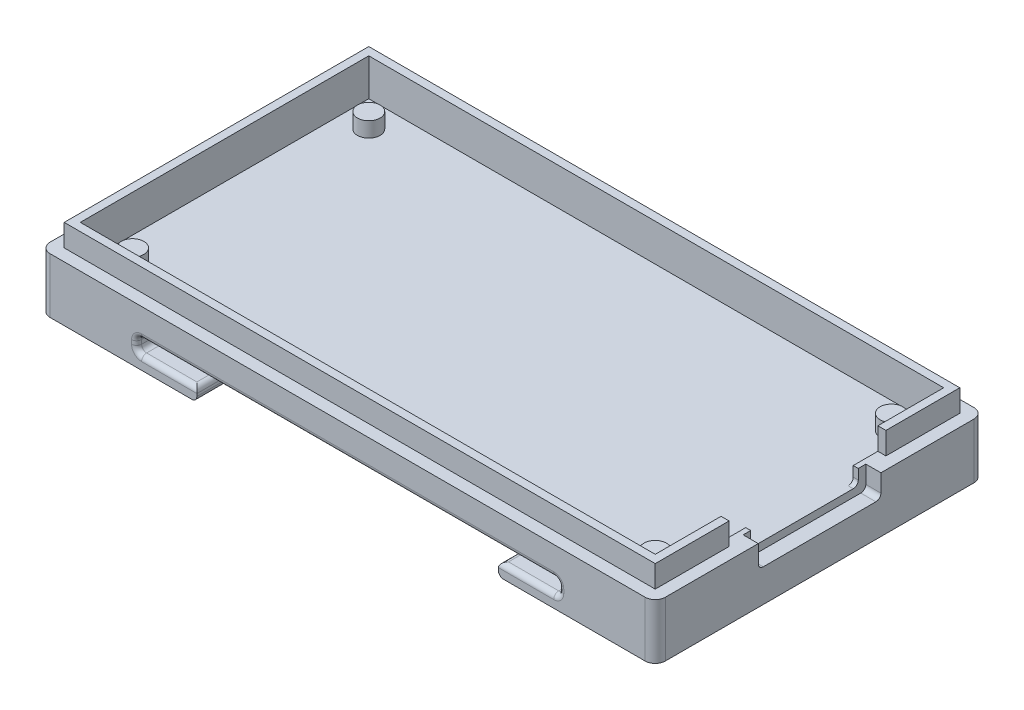
SolidWorks part; units mm, degrees
note: The reader was unsure of these and kept them because the rebuilt part matched: shared geometry of "Sketch2<3>", "Sketch2<4>", "Sketch3<4>", "Sketch2<5>".
ref_plane "Front Plane" through (0, 0, 0) normal (0, 0, 1) x (1, 0, 0)
ref_plane "Top Plane" through (0, 0, 0) normal (0, 1, 0) x (1, 0, 0)
ref_plane "Right Plane" through (0, 0, 0) normal (1, 0, 0) x (0, 0, -1)
sketch "Sketch2" plane through (0, 0, 0) normal (0, 1, 0) x (1, 0, 0)
  line L0 (0, 14.25) -> (0, -14.25) construction
  line L1 (-28.5, -14.25) -> (28.5, -14.25)
  line L2 (-28.5, -14.25) -> (-28.5, 14.25)
  line L3 (-28.5, 14.25) -> (28.5, 14.25)
  line L4 (28.5, -14.25) -> (28.5, 14.25)
  line L5 (-28.5, -14.25) -> (28.5, 14.25) construction
  line L6 (-28.5, 14.25) -> (28.5, -14.25) construction
  line L7 (-28.5, 0) -> (28.5, 0) construction
  line L8 (-30.6, -16.35) -> (-30.6, 16.35)
  line L9 (-28.6, -14.35) -> (28.6, -14.35)
  line L10 (-28.6, -14.35) -> (-28.6, 14.35)
  line L11 (-28.6, 14.35) -> (28.6, 14.35)
  line L12 (28.6, -14.35) -> (28.6, 14.35)
  line L13 (-28.6, -14.35) -> (28.6, 14.35) construction
  line L14 (-28.6, 14.35) -> (28.6, -14.35) construction
  line L15 (-30.6, 16.35) -> (30.6, 16.35)
  line L16 (30.6, -16.35) -> (30.6, 16.35)
  line L17 (-30.6, -16.35) -> (30.6, -16.35)
  line L19 (30.6, -5.35) -> (28.6, -5.35)
  line L20 (30.6, -5.35) -> (30.6, 5.35)
  line L21 (30.6, 5.35) -> (28.6, 5.35)
  line L22 (28.6, -5.35) -> (28.6, 5.35)
  line L31 (-30.6, 16.35) -> (30.6, 16.35) construction
  line L41 (30.6, 6.1) -> (29.1, 6.1)
  line L42 (30.6, 6.1) -> (30.6, -6.1)
  line L43 (30.6, -6.1) -> (29.1, -6.1)
  line L44 (29.1, 6.1) -> (29.1, -6.1)
  circle A0 centre (-26, 11.75) radius 1.125
  circle A1 centre (-26, -11.75) radius 1.125
  circle A2 centre (26, -11.75) radius 1.125
  circle A3 centre (26, 11.75) radius 1.125
  point P0 (0, 0)
  point P18 (0, 0)
  point P31 (30.2961, 16.35)
  dimension "D4" = 2.25
  dimension "D1" = 57
  dimension "D2" = 28.5
  dimension "D3" = 2.5
  dimension "D5" = 2.5
  dimension "D6" = 0.1
  dimension "D7" = 0.1
  dimension "D9" = 9
  dimension "D10" = 9
  dimension "D18" = 0.5
  dimension "D19" = 0.75
  dimension "D20" = 0.75
  dimension "D8" = 2
extrude "Boss-Extrude1" add sketch "Sketch2" along normal blind 1.5
extrude "Boss-Extrude2" add sketch "Sketch2<3>" along normal blind 1.5 from surface at 1.5
sketch "Sketch2<3>" plane through (0, 0, 0) normal (0, 1, 0) x (1, 0, 0) same geometry as "Sketch2"
extrude "Boss-Extrude3" add sketch "Sketch2<4>" against normal blind 2.5
sketch "Sketch2<4>" plane through (0, 0, 0) normal (0, 1, 0) x (1, 0, 0) same geometry as "Sketch2"
fillet "Fillet1" radius 1 4 edges at (-30.6, 0.25, -16.35) (-30.6, 0.25, 16.35) (30.6, 0.25, 16.35) (30.6, 0.25, -16.35)
sketch "Sketch3" plane through (0, 0, 0) normal (0, 0, 1) x (1, 0, 0)
  line L0 (30.6, 3) -> (30.6, -2.5) construction
  line L1 (-21, -1.25) -> (21, -1.25)
  line L2 (-21, -1.25) -> (-21, 0.15)
  line L3 (-21, 0.15) -> (21, 0.15)
  line L4 (21, -1.25) -> (21, 0.15)
  line L5 (-21, -1.25) -> (21, 0.15) construction
  line L6 (-21, 0.15) -> (21, -1.25) construction
  line L7 (30.6, 1.4) -> (-30.6, 1.4)
  line L8 (30.6, 1.4) -> (30.6, -2.5)
  line L9 (30.6, -2.5) -> (-30.6, -2.5)
  line L10 (-30.6, 1.4) -> (-30.6, -2.5)
  line L11 (30.6, 1.4) -> (-30.6, -2.5) construction
  line L12 (30.6, -2.5) -> (-30.6, 1.4) construction
  line L13 (-30.6, -2.5) -> (-30.6, 3) construction
  line L14 (-29.6, -2.5) -> (29.6, -2.5) construction
  line L16 (-10, -1.25) -> (10, -1.25)
  line L17 (-10, -1.25) -> (-10, -2.5)
  line L18 (-10, -2.5) -> (10, -2.5)
  line L19 (10, -1.25) -> (10, -2.5)
  line L20 (15, -2.5) -> (-15, -2.5)
  line L21 (15, -2.5) -> (15, -1.25)
  line L22 (15, -1.25) -> (-15, -1.25)
  line L23 (-15, -2.5) -> (-15, -1.25)
  point P0 (0, -0.55)
  point P5 (0, -0.55)
  point P20 (0, -1.25)
  point P26 (0, -2.5)
  dimension "D1" = 1.25
  dimension "D2" = 1.4
  dimension "D3" = 42
  dimension "D4" = 20
  dimension "D5" = 5
extrude "Cut-Extrude1" cut sketch "Sketch3" against normal through all both and the other way through all contours L1 L4 L3 L2 | L19 L1 L17 L9
ref_plane "Plane1" through (0, 0, -16.35) normal (0, 0, -1) x (-1, 0, 0)
extrude "Cut-Extrude3" cut sketch "Sketch3<4>" against normal through all both and the other way through all contours L9 L21 L1 L19 | L19 L1 L17 L9 | L23 L9 L17 L1
sketch "Sketch3<4>" plane through (0, 0, 0) normal (0, 0, 1) x (1, 0, 0) same geometry as "Sketch3"
fillet "Fillet2" radius 0.5 18 edges at (-18, -1.25, -16.35) (-21, -1.25, 0) (-21, -0.55, 16.35) (-21, 0.15, 0) (0, 0.15, 16.35) (21, 0.15, 0) (21, -0.55, -16.35) (21, -1.25, 0) (-21, -0.55, -16.35) (0, 0.15, -16.35) (-18, -1.25, 16.35) (21, -0.55, 16.35) (18, -1.25, -16.35) (18, -1.25, 16.35) (-15, -1.25, 0) (15, -2.5, 0) (-15, -2.5, 0) (15, -1.25, 0)
extrude "Cut-Extrude2" cut sketch "Sketch2<5>" against normal blind 0.75 and the other way through all from surface contours L41 L44 L21 L16 | L21 L44 L19 L16 | L19 L44 L43 L16
sketch "Sketch2<5>" plane through (0, 0, 0) normal (0, 1, 0) x (1, 0, 0) same geometry as "Sketch2"
fillet "Fillet3" radius 0.5 4 edges at (29.85, 0.75, 6.1) (28.85, 1.5, 5.35) (28.85, 1.5, -5.35) (29.85, 0.75, -6.1)
sketch "Sketch4" plane through (0, 3, 0) normal (0, 1, 0) x (1, 0, 0)
  line L0 (-29.4, 15.15) -> (-29.4, -15.15)
  line L1 (-28.6, 14.35) -> (28.6, 14.35)
  line L2 (-28.6, 14.35) -> (-28.6, -14.35)
  line L3 (-28.6, -14.35) -> (28.6, -14.35)
  line L4 (28.6, 14.35) -> (28.6, -14.35)
  line L5 (-29.4, -15.15) -> (29.4, -15.15)
  line L6 (29.4, 15.15) -> (29.4, -15.15)
  line L7 (-29.4, 15.15) -> (29.4, 15.15)
  line L9 (29.4, 6.1) -> (28.6, 6.1)
  line L10 (29.4, 6.1) -> (29.4, -6.1)
  line L11 (29.4, -6.1) -> (28.6, -6.1)
  line L12 (28.6, 6.1) -> (28.6, -6.1)
  line L13 (29.1, -6.1) -> (30.6, -6.1) construction
  line L14 (29.1, 6.1) -> (30.6, 6.1) construction
  line L15 (29.4, -7.8) -> (28.6, -7.8)
  line L16 (29.4, 7.8) -> (28.6, 7.8)
  line M18 (30.6, -6.1) -> (29.1, -6.1)
  line M22 (28.6, -14.35) -> (-28.6, -14.35)
  line M23 (-28.6, -14.35) -> (-28.6, 14.35)
  line M24 (-28.6, 14.35) -> (28.6, 14.35)
  line M25 (28.6, 14.35) -> (28.6, 5.35)
  line M26 (28.6, 5.35) -> (29.1, 5.35)
  dimension "D2" = 1.7
  dimension "D3" = 1.7
  dimension "D1" = 0.8
extrude "Boss-Extrude4" add sketch "Sketch4" along normal blind 2.2 contours L11 L4 L6 L7 L0 L5 M18 M22 M23 M24 M25 M26
